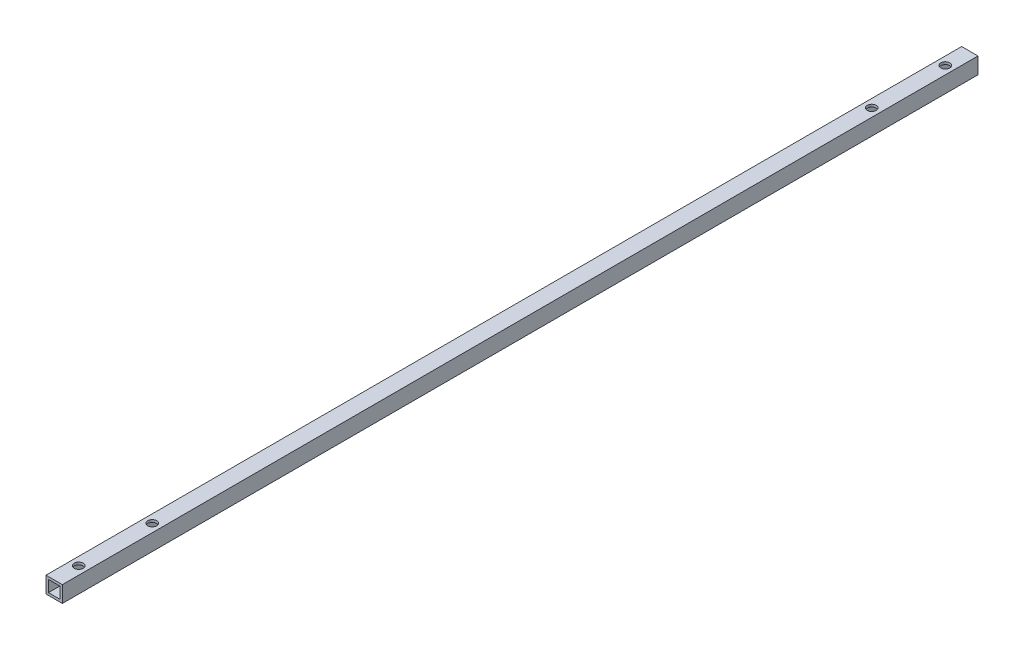
SolidWorks part; units mm, degrees
material "3.0205 (EN AW-1200)"
ref_plane "Ebene vorne" through (0, 0, 0) normal (0, 0, 1) x (1, 0, 0)
ref_plane "Ebene oben" through (0, 0, 0) normal (0, 1, 0) x (1, 0, 0)
ref_plane "Ebene rechts" through (0, 0, 0) normal (1, 0, 0) x (0, 0, -1)
sketch "Skizze1" plane through (0, 0, 0) normal (0, 0, 1) x (1, 0, 0)
  line L1 (5, -5) -> (-5, -5)
  line L2 (5, -5) -> (5, 5)
  line L3 (5, 5) -> (-5, 5)
  line L4 (-5, -5) -> (-5, 5)
  line L5 (5, -5) -> (-5, 5) construction
  line L6 (5, 5) -> (-5, -5) construction
  line L7 (3.5, -3.5) -> (-3.5, -3.5)
  line L8 (3.5, -3.5) -> (3.5, 3.5)
  line L9 (3.5, 3.5) -> (-3.5, 3.5)
  line L10 (-3.5, -3.5) -> (-3.5, 3.5)
  line L11 (3.5, -3.5) -> (-3.5, 3.5) construction
  line L12 (3.5, 3.5) -> (-3.5, -3.5) construction
  point P0 (0, 0)
  point P6 (0, 0)
  dimension "D1" = 10
  dimension "D2" = 1.5
extrude "Aufsatz-Linear austragen1" add sketch "Skizze1" against normal mid plane 560
sketch "Skizze2" plane through (0, 0, 0) normal (0, 1, 0) x (1, 0, 0)
  line L0 (0, -265) -> (0, 265) construction
  line L1 (5, -280) -> (-5, -280) construction
  circle A0 centre (0, -265) radius 2.75
  circle A1 centre (0, 265) radius 2.75
  circle A2 centre (0, -220) radius 2.75
  circle A3 centre (0, 220) radius 2.75
  dimension "D2" = 5.5
  dimension "D1" = 15
  dimension "D3" = 45
  dimension "D4" = 45
extrude "Schnitt-Linear austragen1" cut sketch "Skizze2" against normal mid plane 30
ref_axis "Achse1" through (0, 5.5, 0) along (0, -1, 0)
